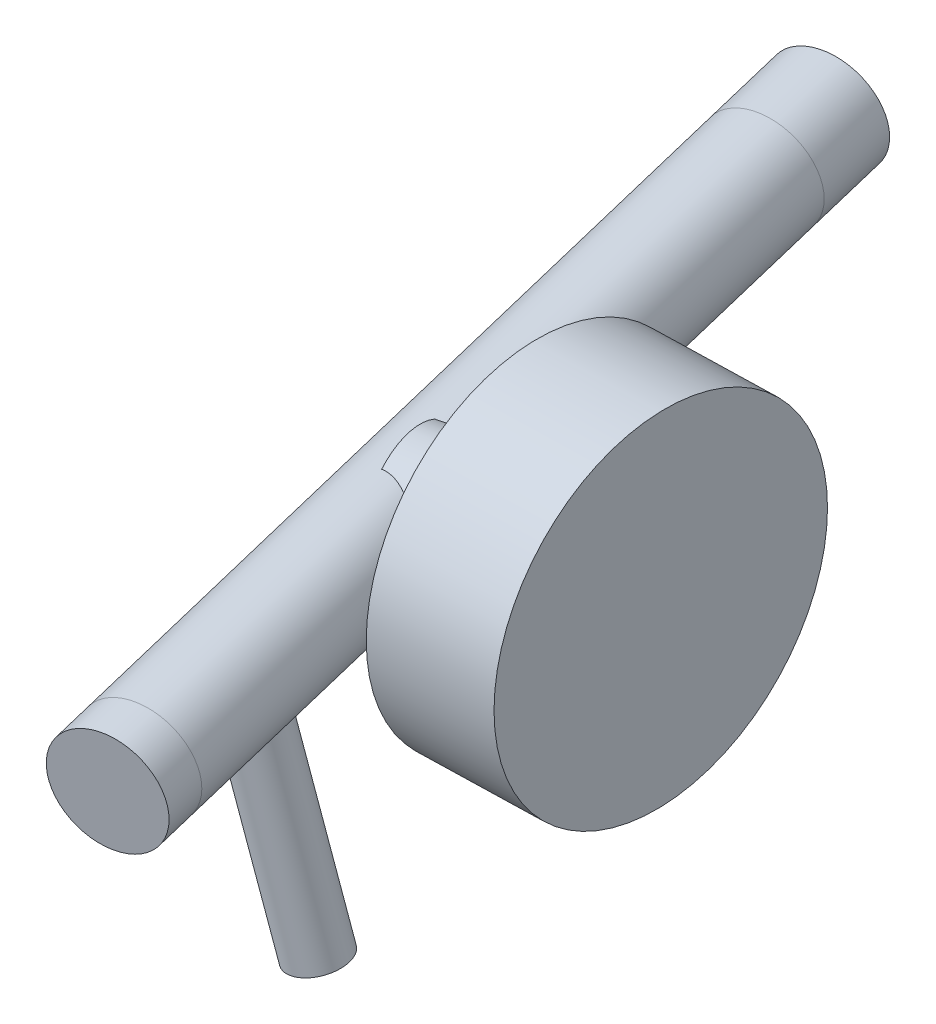
SolidWorks part; units mm, degrees
ref_plane "Plano frontal" through (0, 0, 0) normal (0, 0, 1) x (1, 0, 0)
ref_plane "Plano superior" through (0, 0, 0) normal (0, 1, 0) x (1, 0, 0)
ref_plane "Plano direito" through (0, 0, 0) normal (1, 0, 0) x (0, 0, -1)
sketch3d "SUSP_FR_UCA_ball_joint_eixo"
  line L0 (539.2152, -109.2325, -297.6448) -> (534.717, -107.0006, -323.1553)
sweep "SUSP_FR_UCA_ball_joint" add path "SUSP_FR_UCA_ball_joint_eixo" circular profile diameter 34 parameters "D3"=34
sketch3d "SUSP_FR_LCA_ball_joint_eixo"
  line L0 (584.2491, -131.5771, -42.2448) -> (579.7509, -129.3453, -67.7552)
sweep "SUSP_FR_LCA_ball_joint" add path "SUSP_FR_LCA_ball_joint_eixo" circular profile diameter 34 parameters "D3"=34
sketch3d "SUSP_FR_upright_kingpin_eixo"
  line L0 (582, -130.4612, -55) -> (536.9661, -108.1166, -310.4)
sweep "SUSP_FR_upright_kingpin" add path "SUSP_FR_upright_kingpin_eixo" circular profile diameter 34 parameters "D3"=34
sketch3d "SUSP_FR_upright_spindle_eixo"
  line L0 (563.2747, -121.1702, -161.1964) -> (613.5844, -120.4, -170)
sweep "SUSP_FR_upright_spindle" add path "SUSP_FR_upright_spindle_eixo" circular profile diameter 40 parameters "D3"=40
sketch3d "SUSP_FR_upright_arm_eixo"
  line L0 (575.0797, -127.0275, -94.2469) -> (590.2935, -204.9905, -103.7504)
sweep "SUSP_FR_upright_arm" add path "SUSP_FR_upright_arm_eixo" circular profile diameter 18 parameters "D3"=18
sketch3d "SUSP_FR_hub_eixo"
  line L0 (593.5913, -120.4, -169.4765) -> (633.5776, -120.4, -170.5235)
sweep "SUSP_FR_hub" add path "SUSP_FR_hub_eixo" circular profile diameter 110 parameters "D3"=110
sketch3d "REF_SKETCH"
  line L0 (532.9661, -110.5166, -312.2) -> (540.9661, -105.7166, -308.6)
  line L1 (539.3661, -111.1166, -313.6) -> (534.5661, -105.1166, -307.2)
  line L2 (578, -132.8612, -56.8) -> (586, -128.0612, -53.2)
  line L3 (584.4, -133.4612, -58.2) -> (579.6, -127.4612, -51.8)
  line L4 (586.2935, -207.3905, -105.5504) -> (594.2935, -202.5905, -101.9504)
  line L5 (592.6935, -207.9905, -106.9504) -> (587.8935, -201.9905, -100.5504)
  line L6 (609.5844, -122.8, -171.8) -> (617.5844, -118, -168.2)
  line L7 (615.9844, -123.4, -173.2) -> (611.1844, -117.4, -166.8)
  line L8 (583.5947, -120.4, -169.2147) -> (643.5742, -120.4, -170.7853)
ref_point "P_UBJ"
ref_point "P_LBJ"
ref_point "P_TIE_ROD_OUT"
ref_point "P_WHEEL_CENTER"
ref_axis "A_SPIN" through (583.5947, -120.4, -169.2147) along (0.9997, 0, -0.0262)
